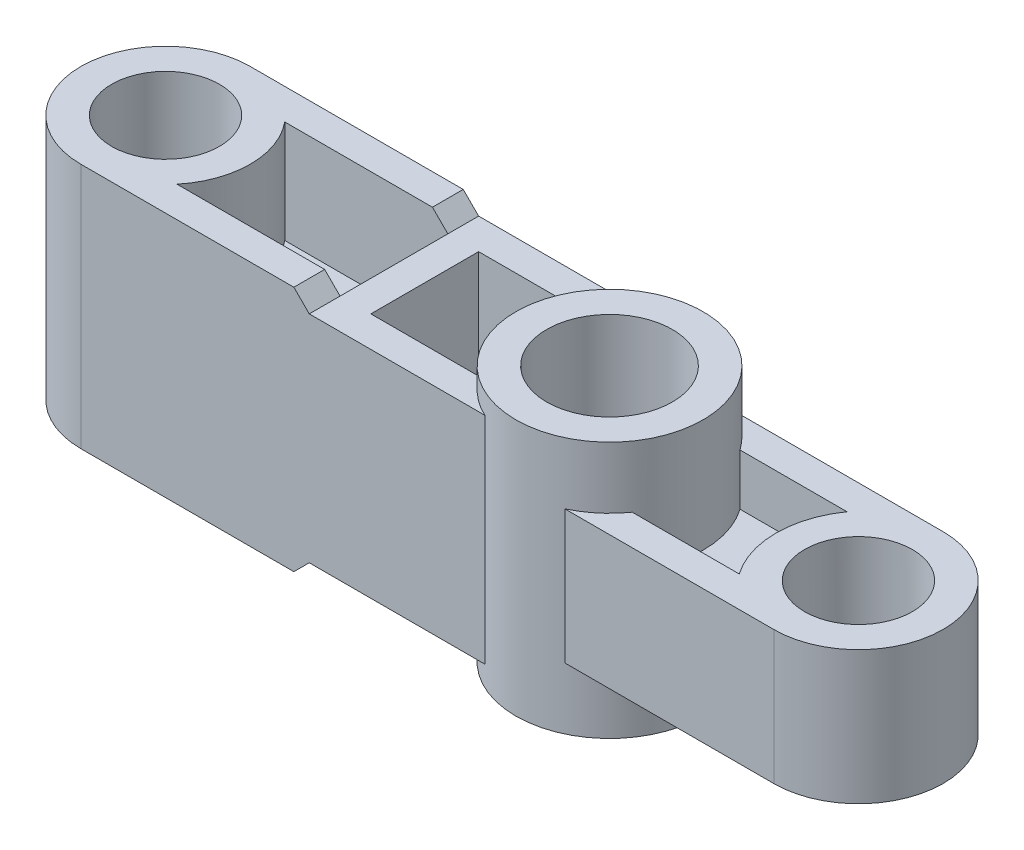
SolidWorks part; units mm, degrees
ref_plane "Front Plane" through (0, 0, 0) normal (0, 0, 1) x (1, 0, 0)
ref_plane "Top Plane" through (0, 0, 0) normal (0, 1, 0) x (1, 0, 0)
ref_plane "Right Plane" through (0, 0, 0) normal (1, 0, 0) x (0, 0, -1)
sketch "Sketch1" plane through (0, 0, 0) normal (0, 1, 0) x (1, 0, 0)
  line L0 (0, 0) -> (50000, 0) construction
  line L1 (16.8, -3.3) -> (-16.8, -3.3) construction
  line L2 (16.8, -3.3) -> (16.8, 3.3) construction
  line L3 (16.8, 3.3) -> (-16.8, 3.3) construction
  line L4 (-16.8, -3.3) -> (-16.8, 3.3) construction
  line L5 (16.8, -3.3) -> (-16.8, 3.3) construction
  line L6 (16.8, 3.3) -> (-16.8, -3.3) construction
  line L7 (0, 0) -> (0, 50000) construction
  line L8 (-13.5, -3.3) -> (13.5, -3.3)
  line L9 (-13.5, 3.3) -> (13.5, 3.3)
  circle A0 centre (13.5, 0) radius 3.3 construction
  circle A1 centre (-13.5, 0) radius 3.3 construction
  arc A2 (-13.5, 3.3) -> (-13.5, -3.3) centre (-13.5, 0) ccw
  arc A3 (13.5, 3.3) -> (13.5, -3.3) centre (13.5, 0) cw
  point P0 (0, 0)
  dimension "D1" = 6.6
  dimension "D2" = 33.6
extrude "Boss-Extrude1" add sketch "Sketch1" along normal blind 9.6 contours A3 L9 A2 L8 region at (0, 0, 0)
sketch "Sketch2" plane through (0, 9.6, 0) normal (0, 1, 0) x (1, 0, 0)
  circle A0 centre (-13.5, 0) radius 2.1
  arc A1 (-13.5, 3.3) -> (-13.5, -3.3) centre (-13.5, 0) ccw construction
  point P5 (-16.8, 0)
  dimension "D1" = 3.3
  dimension "4.2" = 4.2
extrude "Cut-Extrude1" cut sketch "Sketch2" against normal through all
mirror "Mirror1" about plane through (0, 0, 0) normal (1, 0, 0) of "Cut-Extrude1"
ref_plane "Plane1" through (0, 4.8, 0) normal (0, 1, 0) x (1, 0, 0)
sketch "Sketch3" plane through (0, 4.8, 0) normal (0, 1, 0) x (1, 0, 0)
  line L2 (0, 0) -> (-50000, 0) construction
  circle A0 centre (3.8, 0) radius 2.45
  arc A1 (13.5, -3.3) -> (13.5, 3.3) centre (13.5, 0) ccw construction
  circle A2 centre (3.8, 0) radius 3.65
  point P5 (16.8, 0)
  dimension "D1" = 4.9
  dimension "D3" = 7.3
  dimension "D2" = 13
extrude "Boss-Extrude5" add sketch "Sketch3" along normal mid plane 10 contours A2
extrude "Cut-Extrude4" cut sketch "Sketch3<4>" against normal mid plane 10 contours A0
sketch "Sketch3<4>" plane through (0, 4.8, 0) normal (0, 1, 0) x (1, 0, 0) same geometry as "Sketch3"
sketch "Sketch6" plane through (0, 9.6, 0) normal (0, 1, 0) x (1, 0, 0)
  line L0 (-13.5, 3.3) -> (2.2404, 3.3) construction
  line L2 (-4.6, 3.3) -> (-4.6, -3.3)
  line L5 (-13.5, -3.3) -> (2.2404, -3.3) construction
  line L6 (2.2404, 3.3) -> (-4.6, 3.3)
  line L7 (-4.6, -3.3) -> (2.2404, -3.3)
  circle A1 centre (3.8, 0) radius 2.45 construction
  arc A2 (2.2404, 3.3) -> (2.2404, -3.3) centre (3.8, 0) ccw
  arc A3 (2.2404, 3.3) -> (2.2404, -3.3) centre (3.8, 0) ccw construction
  dimension "D1" = 8.4
extrude "Cut-Extrude5" cut sketch "Sketch6" against normal blind 0.6
mirror "Mirror2" about plane through (0, 4.8, 0) normal (0, 1, 0) of "Cut-Extrude5"
sketch "Sketch8" plane through (0, 0, 0) normal (0, -1, 0) x (1, 0, 0)
  line L0 (13.5, 3.3) -> (5.3596, 3.3)
  line L1 (5.3596, -3.3) -> (13.5, -3.3)
  arc A0 (5.3596, 3.3) -> (5.3596, -3.3) centre (3.8, 0) cw
  arc A1 (13.5, 3.3) -> (13.5, -3.3) centre (13.5, 0) cw
  arc A2 (5.3596, -3.3) -> (5.3596, 3.3) centre (3.8, 0) ccw construction
extrude "Cut-Extrude6" cut sketch "Sketch8" against normal blind 2.2
mirror "Mirror3" about plane through (0, 4.8, 0) normal (0, 1, 0) of "Cut-Extrude6"
sketch "Sketch9" plane through (0, 7.4, 0) normal (0, 1, 0) x (1, 0, 0)
  line L0 (13.5, 0) -> (13.5, 50000) construction
  line L1 (13.5, -2.1) -> (50013.5, -2.1) construction
  line L2 (5.3596, 3.3) -> (13.5, 3.3) construction
  line L3 (13.5, 0) -> (10.9544, -2.1) construction
  line L6 (13.5, 3.3) -> (13.5, 2.1) construction
  line L7 (13.5, 2.1) -> (50013.5, 2.1) construction
  line L8 (13.5, 0) -> (10.9544, 2.1) construction
  line L9 (6.7854, 2.1) -> (10.9544, 2.1)
  line L10 (10.9544, -2.1) -> (6.7854, -2.1)
  arc A0 (6.7854, 2.1) -> (6.7854, -2.1) centre (3.8, 0) cw
  circle A1 centre (13.5, 0) radius 2.1 construction
  circle A2 centre (3.8, 0) radius 3.65 construction
  arc A3 (10.9544, 2.1) -> (10.9544, -2.1) centre (13.9398, 0) ccw
  dimension "D1" = 3.3
extrude "Cut-Extrude7" cut sketch "Sketch9" against normal blind 2
mirror "Mirror4" about plane through (0, 4.8, 0) normal (0, 1, 0) of "Cut-Extrude7"
sketch "Sketch11" plane through (0, 9.6, 0) normal (0, 1, 0) x (1, 0, 0)
  line L0 (-13.5, -2.1) -> (49986.5, -2.1) construction
  line L1 (-13.5, 2.1) -> (49986.5, 2.1) construction
  line L2 (-13.5, 0) -> (-10.9544, 2.1) construction
  line L3 (-13.5, 0) -> (-10.9544, -2.1) construction
  line L4 (-10.9544, 2.1) -> (-4.6, 2.1)
  line L5 (-4.6, 3.3) -> (-4.6, -3.3) construction
  line L6 (-4.6, 2.1) -> (-4.6, -2.1)
  line L7 (-4.6, -2.1) -> (-10.9544, -2.1)
  circle A2 centre (-13.5, 0) radius 2.1 construction
  arc A3 (-10.9544, 2.1) -> (-10.9544, -2.1) centre (-13.5, 0) cw
  dimension "D2" = 3.3
  dimension "D1" = 3.3
extrude "Cut-Extrude8" cut sketch "Sketch11" against normal blind 4
mirror "Mirror7" about plane through (0, 4.8, 0) normal (0, 1, 0) of "Cut-Extrude8"
chamfer "Chamfer1" distance 0.6 4 edges at (-4.6, 9.6, 2.7) (-4.6, 9.6, -2.7) (-4.6, 0, -2.7) (-4.6, 0, 2.7)
sketch "Sketch13" plane through (0, 9, 0) normal (0, 1, 0) x (1, 0, 0)
  line L0 (-10.9544, -2.1) -> (-4.6, -2.1) construction
  line L1 (-4.6, 2.1) -> (-3.4, 2.1) construction
  line L2 (-4.6, 2.1) -> (-4.6, -2.1) construction
  line L3 (-4.6, -2.1) -> (-3.4, -2.1) construction
  line L4 (-3.4, 2.1) -> (-3.4, -2.1) construction
  line L5 (0.8146, -2.1) -> (-3.4, -2.1)
  line L10 (-3.4, -2.1) -> (-3.4, 2.1)
  line L11 (-3.4, 2.1) -> (0.8146, 2.1)
  arc A0 (2.2404, 3.3) -> (2.2404, -3.3) centre (3.8, 0) ccw construction
  circle A1 centre (3.8, 0) radius 3.65 construction
  arc A2 (0.8146, 2.1) -> (0.8146, -2.1) centre (3.8, 0) ccw
  dimension "D1" = 1.2
extrude "Cut-Extrude9" cut sketch "Sketch13" against normal through all
